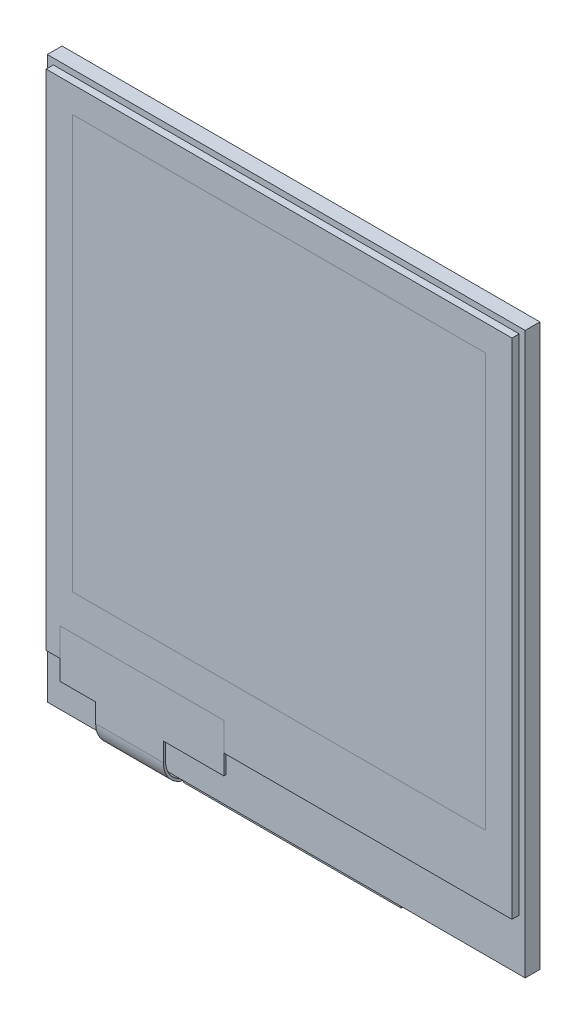
SolidWorks part; units mm, degrees
ref_plane "前视基准面" through (0, 0, 0) normal (0, 0, 1) x (1, 0, 0)
ref_plane "上视基准面" through (0, 0, 0) normal (0, 1, 0) x (1, 0, 0)
ref_plane "右视基准面" through (0, 0, 0) normal (1, 0, 0) x (0, 0, -1)
sketch "草图1" plane through (0, 0, 0) normal (0, 0, 1) x (1, 0, 0)
  line L1 (15.9, -18.66) -> (-15.9, -18.66)
  line L2 (15.9, -18.66) -> (15.9, 18.66)
  line L3 (15.9, 18.66) -> (-15.9, 18.66)
  line L4 (-15.9, -18.66) -> (-15.9, 18.66)
  line L5 (15.9, -18.66) -> (-15.9, 18.66) construction
  line L6 (15.9, 18.66) -> (-15.9, -18.66) construction
  point P0 (0, 0)
  dimension "D1" = 31.8
  dimension "D2" = 37.32
extrude "凸台-拉伸1" add sketch "草图1" along normal blind 0.98
sketch "草图2" plane through (0, 0, 0.98) normal (0, 0, 1) x (1, 0, 0)
  line L0 (0, 18.26) -> (0, 0) construction
  line L1 (-15.5, 18.26) -> (15.5, 18.26)
  line L2 (-15.5, 18.26) -> (-15.5, -15.24)
  line L3 (-15.5, -15.24) -> (15.5, -15.24)
  line L4 (15.5, 18.26) -> (15.5, -15.24)
  line L5 (15.9, 18.66) -> (-15.9, 18.66) construction
  dimension "D1" = 31
  dimension "D2" = 33.5
  dimension "D3" = 0.4
extrude "凸台-拉伸2" add sketch "草图2" along normal blind 1.46 from surface starting at face at (0, 0, 0)
sketch "草图5" plane through (0, 0, 1.46) normal (0, 0, 1) x (1, 0, 0)
  line L0 (-14.57, -15.24) -> (-14.57, -16.56)
  line L1 (-15.5, -15.24) -> (15.5, -15.24) construction
  line L2 (-14.57, -16.56) -> (-12.2, -16.56)
  line L3 (-12.2, -16.56) -> (-12.2, -17.06)
  line L4 (-12.2, -17.06) -> (-7.7, -17.06)
  line L5 (-7.7, -17.06) -> (-7.7, -16.56)
  line L6 (-7.7, -16.56) -> (-3.67, -16.56)
  line L7 (-3.67, -16.56) -> (-3.67, -15.24)
  line L8 (15.5, -15.24) -> (-15.5, -15.24) construction
  line L9 (-3.67, -15.24) -> (-14.57, -15.24)
  line L10 (-15.9, 18.66) -> (-15.9, -18.66) construction
  line L11 (-15.9, -18.66) -> (15.9, -18.66) construction
  point P7 (-14.57, -15.9)
  dimension "D1" = 10.9
  dimension "D2" = 1.33
  dimension "D3" = 3.7
  dimension "D4" = 4.5
  dimension "D5" = 2.1
  dimension "D6" = 0.5
extrude "凸台-拉伸3" add sketch "草图5" against normal blind 0.15
sketch "草图6" plane through (0, 0, 0.98) normal (0, 0, 1) x (1, 0, 0)
  line L0 (-15.9, -18.66) -> (15.9, -18.66) construction
  line L1 (-7.25, -18.66) -> (7.25, -18.66)
  line L2 (-7.25, -18.66) -> (-7.25, -19.16)
  line L3 (-7.25, -19.16) -> (7.25, -19.16)
  line L4 (7.25, -18.66) -> (7.25, -19.16)
  line L5 (0, 0) -> (0, -18.66) construction
  dimension "D1" = 14.5
  dimension "D2" = 0.5
extrude "凸台-拉伸4" add sketch "草图6" against normal blind 0.15 from offset 0.4 offset against normal yes
sketch "草图7" plane through (0, 0, 1.46) normal (0, 0, 1) x (1, 0, 0)
  line L0 (0, 2.765) -> (0, 0) construction
  line L1 (13.755, -10.99) -> (-13.755, -10.99)
  line L2 (13.755, -10.99) -> (13.755, 16.52)
  line L3 (13.755, 16.52) -> (-13.755, 16.52)
  line L4 (-13.755, -10.99) -> (-13.755, 16.52)
  line L5 (13.755, -10.99) -> (-13.755, 16.52) construction
  line L6 (13.755, 16.52) -> (-13.755, -10.99) construction
  line L7 (15.9, 18.66) -> (-15.9, 18.66) construction
  point P0 (0, 2.765)
  dimension "D1" = 27.51
  dimension "D2" = 2.14
wrap "包覆1" sketch "草图7" wrap type scribe source sketch "草图7"
sketch "草图9" plane through (0, 0, 1.46) normal (0, 0, 1) x (1, 0, 0)
  line L0 (-14.57, -15.24) -> (-14.57, -13.36)
  line L1 (-14.57, -13.36) -> (-3.67, -13.36)
  line L2 (-3.67, -13.36) -> (-3.67, -15.24)
  line L3 (-3.67, -16.56) -> (-3.67, -15.24) construction
  line L4 (-7.7, -16.56) -> (-3.67, -16.56) construction
  line L5 (-7.7, -17.06) -> (-7.7, -16.56) construction
  line L6 (-12.2, -17.06) -> (-7.7, -17.06) construction
  line L7 (-12.2, -16.56) -> (-12.2, -17.06) construction
  line L8 (-14.57, -16.56) -> (-12.2, -16.56) construction
  line L9 (-14.57, -15.24) -> (-14.57, -16.56) construction
  line L10 (-3.67, -16.56) -> (-3.67, -15.24)
  line L11 (-7.7, -16.56) -> (-3.67, -16.56)
  line L12 (-7.7, -17.06) -> (-7.7, -16.56)
  line L13 (-12.2, -17.06) -> (-7.7, -17.06)
  line L14 (-12.2, -16.56) -> (-12.2, -17.06)
  line L15 (-14.57, -16.56) -> (-12.2, -16.56)
  line L16 (-14.57, -15.24) -> (-14.57, -16.56)
  dimension "D1" = 3.2
wrap "包覆2" sketch "草图9" wrap type scribe source sketch "草图9"
sketch "草图10" plane through (-12.2, 0, 0) normal (-1, 0, 0) x (0, 0, 1)
  line L0 (1.46, -17.06) -> (1.46, -17.81)
  line L1 (-2.04, -17.81) -> (-2.04, -17.31)
  line L2 (0.98, -18.66) -> (0, -18.66) construction
  arc A0 (1.46, -17.81) -> (-2.04, -17.81) centre (-0.29, -17.81) cw
  dimension "D2" = 1.75
  dimension "D1" = 0.75
  dimension "D3" = 1.35
extrude "拉伸-薄壁1" add sketch "草图10" against normal up to surface (4.5 mm away) thin thin type one direction wall 0.15
